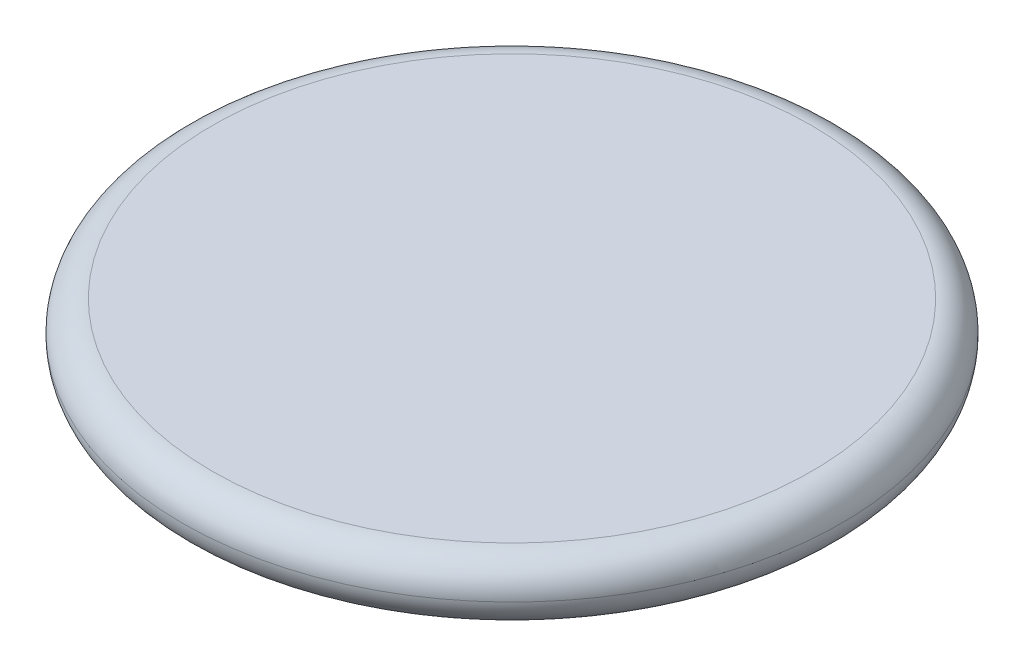
SolidWorks part; units mm, degrees
ref_plane "Front Plane" through (0, 0, 0) normal (0, 0, 1) x (1, 0, 0)
ref_plane "Top Plane" through (0, 0, 0) normal (0, 1, 0) x (1, 0, 0)
ref_plane "Right Plane" through (0, 0, 0) normal (1, 0, 0) x (0, 0, -1)
sketch "Sketch2" plane through (0, 0, 0) normal (0, 1, 0) x (1, 0, 0)
  circle A0 centre (0, 0) radius 220
extrude "Boss-Extrude1" add sketch "Sketch2" along normal blind 20 and the other way blind 20 contours A0
fillet "Fillet1" radius 20 2 edges at (0, -20, 220) (0, 20, 220)
